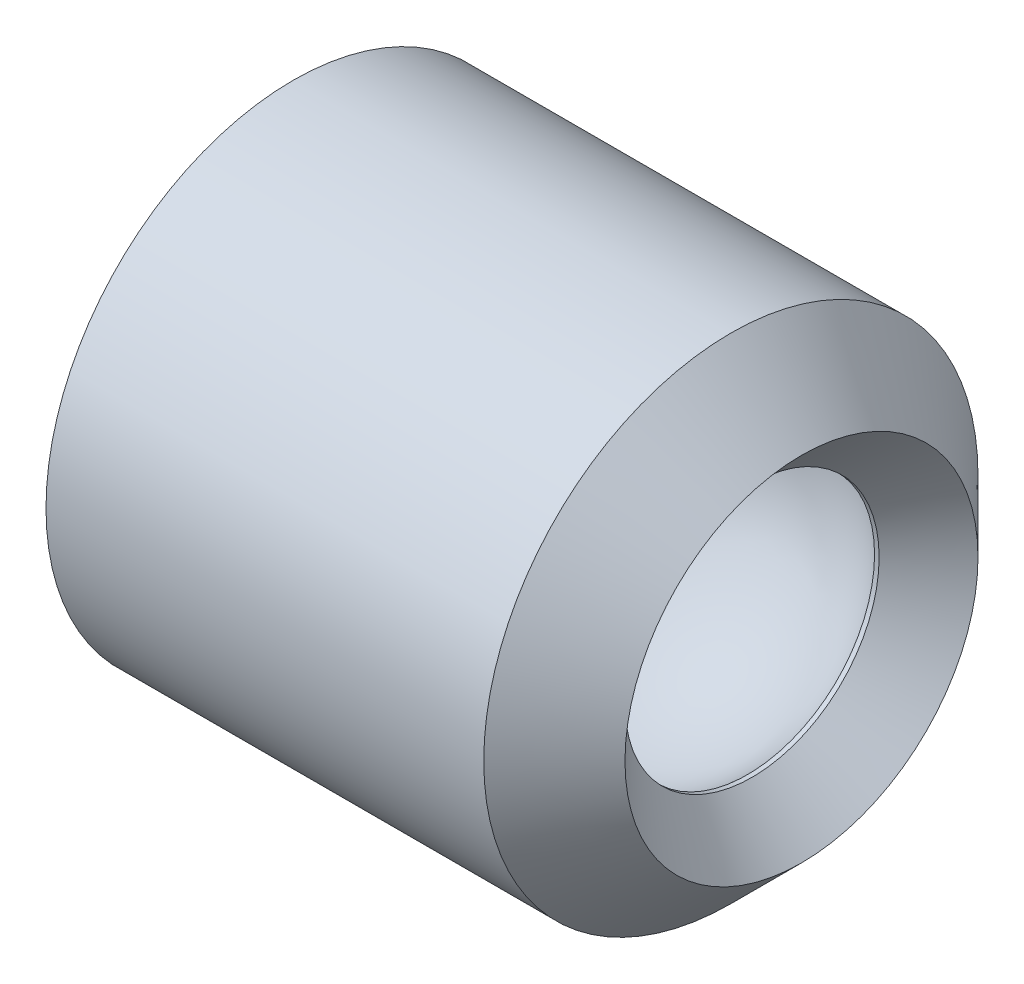
SolidWorks part; units mm, degrees
ref_plane "Płaszczyzna przednia" through (0, 0, 0) normal (0, 0, 1) x (1, 0, 0)
ref_plane "Płaszczyzna górna" through (0, 0, 0) normal (0, 1, 0) x (1, 0, 0)
ref_plane "Płaszczyzna prawa" through (0, 0, 0) normal (1, 0, 0) x (0, 0, -1)
sketch "Szkic1" plane through (0, 0, 0) normal (1, 0, 0) x (0, 0, -1)
  circle A0 centre (0, 0) radius 17.5
  dimension "D1" = 35
extrude "Dodanie-wyciągnięcie1" add sketch "Szkic1" along normal blind 36
sketch "Szkic2" plane through (0, 0, 0) normal (-1, 0, 0) x (0, 0, 1)
  circle A0 centre (0, 0) radius 6
  dimension "D1" = 12
extrude "Wytnij-wyciągnięcie1" cut sketch "Szkic2" against normal blind 10
thread "Gwint1" pitch 1.5 method extrude profile "Profil gwintu1" start angle 0, offset 0, length 10, pitch 1.5, diameter 12
ref_plane "Płaszczyzna1" through (0, 0, -6) normal (0, -1, 0) x (0, 0, -1)
sketch "Profil gwintu1" plane through (0, 0, -6) normal (0, -1, 0) x (0, 0, -1)
  line L0 (0, 0) -> (0, 1.5) construction
  line L11 (0, 0) -> (0, 1.3125)
  line L12 (0, 1.3125) -> (-0.8119, 0.8437)
  line L13 (-0.8119, 0.8437) -> (-0.8119, 0.4687)
  line L15 (-0.8119, 0.4687) -> (0, 0)
  line L17 (-0.8119, 0.6562) -> (0, 0.6562) construction
  point P2 (0, 0)
  dimension "Pitch" = 1.5
  dimension "Profile_Angle" = 60
  dimension "Profile_Land" = 0.375
  dimension "Profile_Height" = 0.8119
sketch "Szkic6" plane through (0, 0, 0) normal (0, 0, 1) x (1, 0, 0)
  line L0 (0, 0) -> (36, 0) construction
  line L1 (36, -17.5) -> (36, 17.5) construction
  line L2 (36, -17.5) -> (36, 17.5) construction
  line L3 (23.5, 12.5) -> (23.5, -12.5)
  arc A0 (23.5, -12.5) -> (23.5, 12.5) centre (23.5, 0) ccw
  dimension "D1" = 25
chamfer "Sfazowanie1" distance 5 angle 45 1 edges at (36, 0, -17.5)
sketch "Szkic7" plane through (36, 0, 0) normal (1, 0, 0) x (0, 0, -1)
  circle A0 centre (0, 0) radius 9
  dimension "D1" = 18
extrude "Wytnij-wyciągnięcie2" cut sketch "Szkic7" against normal blind 11
chamfer "Sfazowanie3" distance 3.5 angle 45 1 edges at (36, 0, -9)
revolve "Wycięcie-obrót13" cut sketch "Szkic6" angle 360 about L3 region at (28.8052, 5.3052, 0) region at (28.8052, -5.3052, 0)
